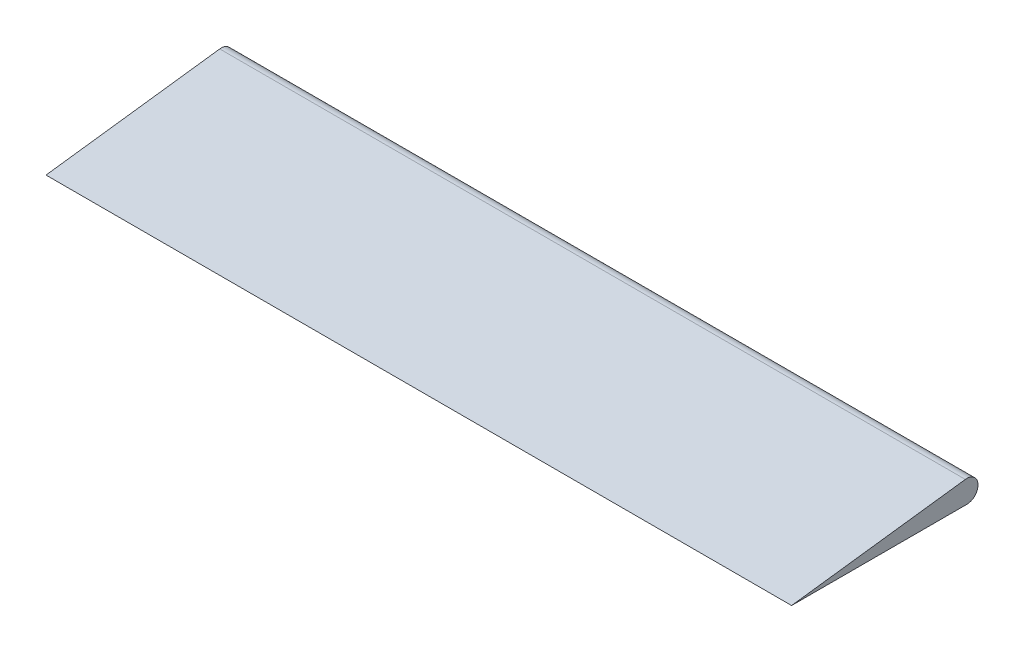
SolidWorks part; units mm, degrees
ref_plane "Front Plane" through (0, 0, 0) normal (0, 0, 1) x (1, 0, 0)
ref_plane "Top Plane" through (0, 0, 0) normal (0, 1, 0) x (1, 0, 0)
ref_plane "Right Plane" through (0, 0, 0) normal (1, 0, 0) x (0, 0, -1)
sketch "Sketch1" plane through (0, 0, 0) normal (1, 0, 0) x (0, 0, -1)
  line L0 (0, 0) -> (234.9384, 0)
  line L1 (0, 0) -> (233.0151, 30)
  line L2 (250, 814.8547) -> (250, -450.4019) construction
  arc A0 (233.0151, 30) -> (234.9384, 0) centre (234.9384, 15.0616) cw
  dimension "D1" = 250
  dimension "D2" = 30
extrude "Boss-Extrude1" add sketch "Sketch1" along normal blind 1000
